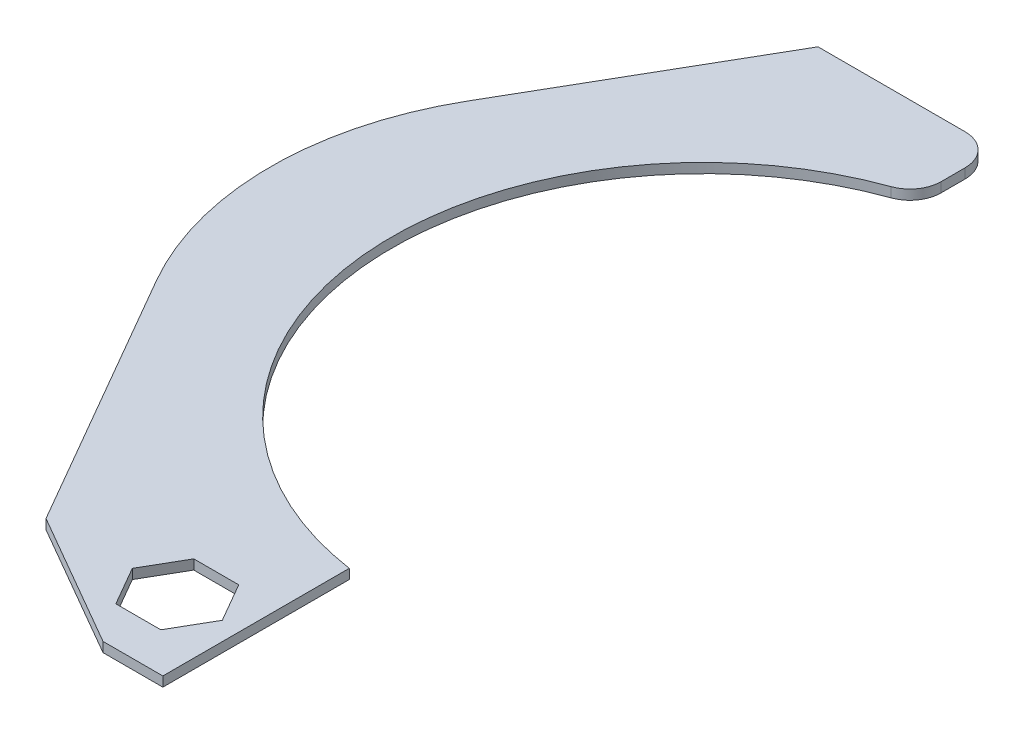
SolidWorks part; units mm, degrees
ref_plane "Front Plane" through (0, 0, 0) normal (0, 0, 1) x (1, 0, 0)
ref_plane "Top Plane" through (0, 0, 0) normal (0, 1, 0) x (1, 0, 0)
ref_plane "Right Plane" through (0, 0, 0) normal (1, 0, 0) x (0, 0, -1)
sketch "Sketch1" plane through (0, 0, 0) normal (0, 1, 0) x (1, 0, 0)
  line L1 (-78.443, 0) -> (-39.2215, -67.9336)
  line L5 (-13.8215, 67.9336) -> (-39.2215, 67.9336) construction
  line L6 (-42.8877, 61.5836) -> (-78.443, 0)
  line L8 (-7.4715, -50.2476) -> (-7.4715, -67.9336)
  line L9 (-13.8215, 61.5836) -> (-42.8877, 61.5836)
  line L10 (78.443, 0) -> (58.8322, 33.9668) [skipped]
  line L11 (39.2215, -67.9336) -> (58.8322, -33.9668) [skipped]
  line L13 (-39.2215, -67.9336) -> (-39.2215, -80.6336)
  line L14 (-39.2215, -80.6336) -> (-7.4715, -80.6336)
  line L15 (-7.4715, -67.9336) -> (-7.4715, -80.6336)
  line L16 (-39.2215, -67.9336) -> (-13.8215, -67.9336) [skipped]
  line L17 (-13.8215, 61.5836) -> (-13.8215, 48.8836)
  line L18 (-13.8215, 67.9336) -> (-13.8215, 66.5127) construction
  line L19 (-13.8215, 66.5127) -> (-13.8215, 61.5836) construction
  line L20 (-39.2215, 67.9336) -> (-42.8877, 61.5836) construction
  arc A0 (-13.8215, 48.8836) -> (-7.4715, -50.2476) centre (0, 0) ccw
  arc A1 (-13.8215, 66.5127) -> (-7.4715, -67.5215) centre (0, 0) ccw construction
  dimension "D1" = 101.6
  dimension "D2" = 19.05
  dimension "D3" = 25.4
  dimension "D4" = 12.7
  dimension "D5" = 12.7
  dimension "D6" = 31.75
  dimension "D7" = 12.7
extrude "Boss-Extrude1" add sketch "Sketch1" along normal blind 1.5875
sketch "Sketch2" plane through (0, 1.5875, 0) normal (0, 1, 0) x (1, 0, 0)
  line L0 (-39.2215, -67.9336) -> (-17.8181, -67.9336) construction
  line L1 (-10.4858, -67.9336) -> (-14.1519, -61.5836)
  line L2 (-14.1519, -61.5836) -> (-21.4843, -61.5836)
  line L3 (-21.4843, -61.5836) -> (-25.1504, -67.9336)
  line L4 (-25.1504, -67.9336) -> (-21.4843, -74.2836)
  line L5 (-21.4843, -74.2836) -> (-14.1519, -74.2836)
  line L6 (-14.1519, -74.2836) -> (-10.4858, -67.9336)
  line L7 (-39.2215, -67.9336) -> (-39.2215, -80.6336) construction
  line L8 (-17.8181, -67.9336) -> (0, -67.9336) construction
  line L10 (-39.2215, -80.6336) -> (-7.4715, -80.6336) construction
  line L11 (0, 0) -> (0, -67.9336) construction
  circle A0 centre (-17.8181, -67.9336) radius 6.35 construction
  dimension "D1" = 12.7
  dimension "D2" = 17.8181
  dimension "D3" = 12.7
extrude "Cut-Extrude1" cut sketch "Sketch2" against normal blind 1.5875
fillet "Fillet1" radius 5.08 2 edges at (-13.8215, 0.7937, -48.8836) (-13.8215, 0.7937, -61.5836)
chamfer "Chamfer1" distance 12.7 angle 60 1 edges at (-39.2215, 0.7937, 80.6336) first distance on face at (-39.2215, 0.7937, 74.2836)
fillet "Fillet2" radius 50.8 1 edges at (-78.443, 0.7937, 0)
